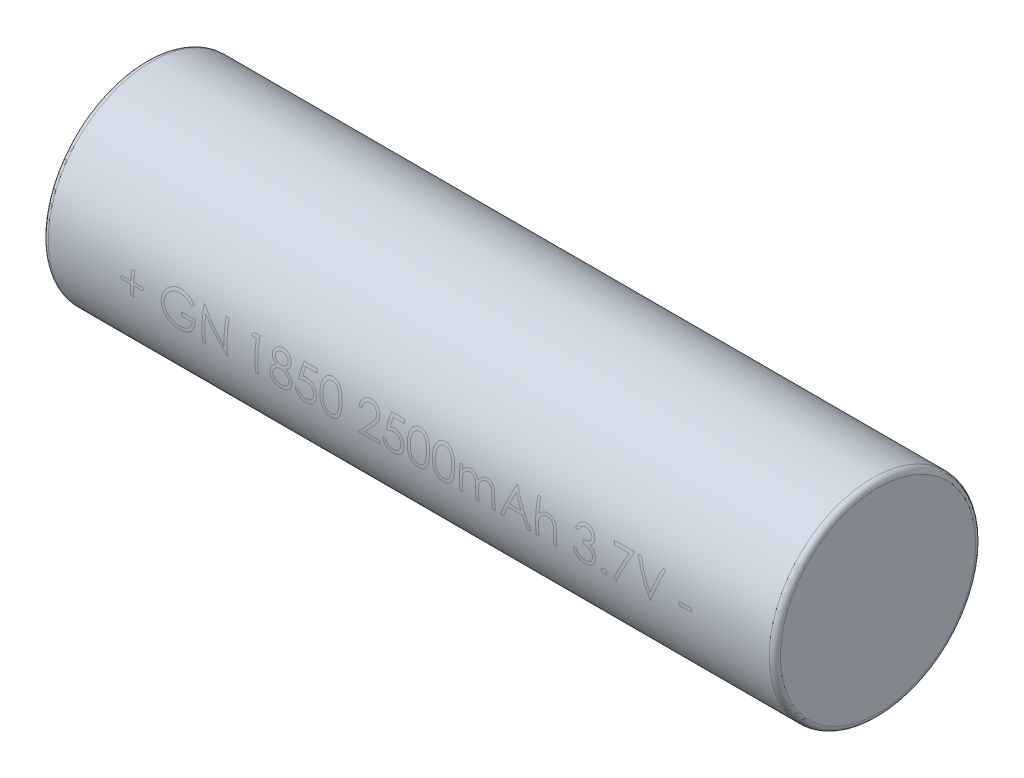
SolidWorks part; units mm, degrees
ref_plane "Alzado" through (0, 0, 0) normal (0, 0, 1) x (1, 0, 0)
ref_plane "Planta" through (0, 0, 0) normal (0, 1, 0) x (1, 0, 0)
ref_plane "Vista lateral" through (0, 0, 0) normal (1, 0, 0) x (0, 0, -1)
sketch "Croquis2" plane through (0, 0, 0) normal (1, 0, 0) x (0, 0, -1)
  circle A0 centre (0, 0) radius 9.25
  dimension "D1" = 18.5
extrude "Saliente-Extruir1" add sketch "Croquis2" along normal mid plane 65.6
fillet "Redondeo1" radius 0.5 2 edges at (-32.8, 0, -9.25) (32.8, 0, -9.25)
sketch "Croquis3" plane through (-32.8, 0, 0) normal (-1, 0, 0) x (0, 0, 1)
  circle A0 centre (0, 0) radius 3
  dimension "D1" = 6
extrude "Saliente-Extruir2" add sketch "Croquis3" along normal mid plane 2
fillet "Redondeo2" radius 1 1 edges at (-33.8, 0, 3)
ref_plane "Plano1" through (0, 0, 9.25) normal (0, 0, 1) x (1, 0, 0)
sketch "Croquis4" plane through (0, 0, 9.25) normal (0, 0, 1) x (1, 0, 0)
  text T0 "+ GN 1850 2500mAh 3.7V -" font "Century Gothic" height in points 11
split line "Línea de partición1"
